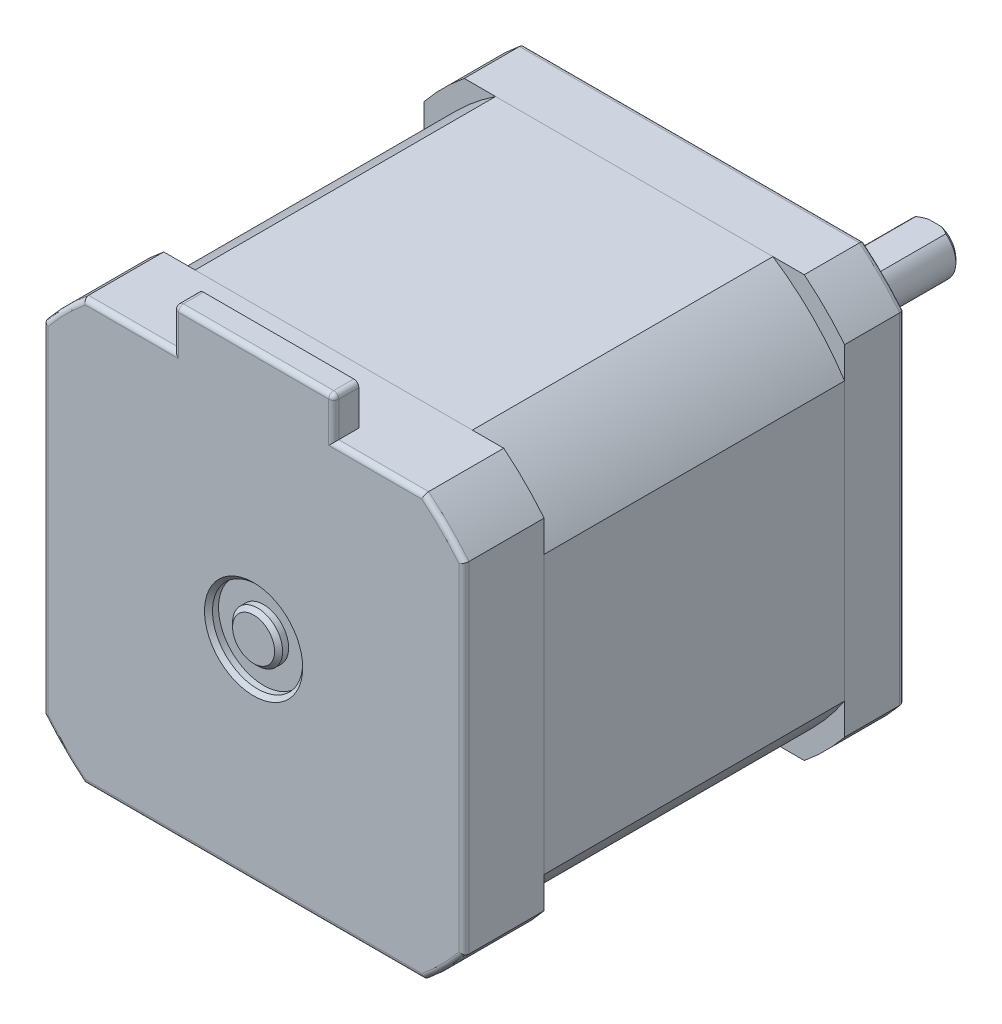
SolidWorks part; units mm, degrees
ref_plane "Plan de face" through (0, 0, 0) normal (0, 0, 1) x (1, 0, 0)
ref_plane "Plan de dessus" through (0, 0, 0) normal (0, 1, 0) x (1, 0, 0)
ref_plane "Plan de droite" through (0, 0, 0) normal (1, 0, 0) x (0, 0, -1)
sketch "Esquisse1" plane through (0, 0, 0) normal (0, 0, 1) x (1, 0, 0)
  line L0 (21, 16.9706) -> (21, -16.9706)
  line L1 (-21, 21) -> (21, 21) construction
  line L2 (-21, 21) -> (-21, -21) construction
  line L3 (-21, -21) -> (21, -21) construction
  line L4 (21, 21) -> (21, -21) construction
  line L5 (-21, 21) -> (21, -21) construction
  line L6 (-21, -21) -> (21, 21) construction
  line L7 (16.9706, -21) -> (-16.9706, -21)
  line L8 (-21, -16.9706) -> (-21, 16.9706)
  line L9 (-16.9706, 21) -> (16.9706, 21)
  arc A0 (-16.9706, 21) -> (-21, 16.9706) centre (0, 0) ccw
  arc A1 (21, 16.9706) -> (16.9706, 21) centre (0, 0) ccw
  arc A2 (-21, -16.9706) -> (-16.9706, -21) centre (0, 0) ccw
  arc A3 (16.9706, -21) -> (21, -16.9706) centre (0, 0) ccw
  point P0 (0, 0)
  dimension "D2" = 54
  dimension "D1" = 42
extrude "Boss.-Extru.1" add sketch "Esquisse1" along normal blind 6
sketch "Esquisse2" plane through (0, 0, 6) normal (0, 0, 1) x (1, 0, 0)
  line L23 (-13.8392, 21) -> (13.8392, 21)
  line L24 (16.9706, 21) -> (-16.9706, 21) construction
  line L25 (21, 13.8392) -> (21, -13.8392)
  line L26 (21, -16.9706) -> (21, 16.9706) construction
  line L27 (13.8392, -21) -> (-13.8392, -21)
  line L28 (-16.9706, -21) -> (16.9706, -21) construction
  line L29 (-21, -13.8392) -> (-21, 13.8392)
  line L30 (-21, 16.9706) -> (-21, -16.9706) construction
  arc A60 (-13.8392, 21) -> (-21, 13.8392) centre (0, 0) ccw
  arc A61 (21, 16.9706) -> (16.9706, 21) centre (0, 0) ccw construction
  arc A62 (21, 13.8392) -> (13.8392, 21) centre (0, 0) ccw
  arc A63 (13.8392, -21) -> (21, -13.8392) centre (0, 0) ccw
  arc A64 (-21, -13.8392) -> (-13.8392, -21) centre (0, 0) ccw
  dimension "D1" = 1.85
extrude "Boss.-Extru.2" add sketch "Esquisse2" along normal blind 30 separate body
sketch "Esquisse3" plane through (0, 0, 36) normal (0, 0, 1) x (1, 0, 0)
  line L0 (-16.9706, -21) -> (16.9706, -21) construction
  line L1 (21, -16.9706) -> (21, 16.9706) construction
  line L2 (16.9706, 21) -> (-16.9706, 21) construction
  line L3 (-21, 16.9706) -> (-21, -16.9706) construction
  line L4 (-16.9706, -21) -> (16.9706, -21)
  line L5 (21, -16.9706) -> (21, 16.9706)
  line L6 (16.9706, 21) -> (-16.9706, 21)
  line L7 (-21, 16.9706) -> (-21, -16.9706)
  arc A0 (-21, -16.9706) -> (-16.9706, -21) centre (0, 0) ccw construction
  arc A1 (16.9706, -21) -> (21, -16.9706) centre (0, 0) ccw construction
  arc A2 (21, 16.9706) -> (16.9706, 21) centre (0, 0) ccw construction
  arc A3 (-16.9706, 21) -> (-21, 16.9706) centre (0, 0) ccw construction
  arc A4 (-21, -16.9706) -> (-16.9706, -21) centre (0, 0) ccw
  arc A5 (16.9706, -21) -> (21, -16.9706) centre (0, 0) ccw
  arc A6 (21, 16.9706) -> (16.9706, 21) centre (0, 0) ccw
  arc A7 (-16.9706, 21) -> (-21, 16.9706) centre (0, 0) ccw
extrude "Boss.-Extru.3" add sketch "Esquisse3" along normal blind 8 separate body
sketch "Esquisse4" plane through (0, 21, 0) normal (0, 1, 0) x (1, 0, 0)
  line L0 (16.9706, -44) -> (-16.9706, -44) construction
  line L1 (8, -44) -> (-8, -44)
  line L2 (8, -44) -> (8, -41.5)
  line L3 (8, -41.5) -> (-8, -41.5)
  line L4 (-8, -44) -> (-8, -41.5)
  line L5 (0, 0) -> (0, -41.5) construction
  dimension "D1" = 2.5
  dimension "D2" = 16
extrude "Boss.-Extru.4" add sketch "Esquisse4" along normal blind 4
sketch "Esquisse5" plane through (0, 0, 0) normal (1, 0, 0) x (0, 0, -1)
  line L0 (0, 0) -> (-78.698, 0) construction
  line L2 (2, 11) -> (0, 11)
  line L3 (2, 11) -> (2, 4.5)
  line L4 (2, 4.5) -> (0, 4.5)
  line L5 (0, 11) -> (0, 4.5)
  line L6 (0, -16.9706) -> (0, 16.9706) construction
  line L7 (24, 0) -> (0, 0)
  line L8 (24, 0) -> (24, 2.5)
  line L9 (24, 2.5) -> (0, 2.5)
  line L10 (0, 0) -> (0, 2.5)
  dimension "D1" = 2
  dimension "D2" = 22
  dimension "D3" = 9
  dimension "D4" = 5
  dimension "D5" = 24
revolve "Révolution1" add sketch "Esquisse5" angle 360 about L0
fillet "Congé1" radius 0.5 14 edges at (-21, 0, 44) (-19.0919, 19.0919, 44) (-12.4853, 21, 44) (-8, 23, 44) (0, 25, 44) (8, 23, 44) (12.4853, 21, 44) (19.0919, 19.0919, 44) (21, 0, 44) (19.0919, -19.0919, 44) (0, -21, 44) (-19.0919, -19.0919, 44) (-8, 25, 42.75) (8, 25, 42.75)
fillet "Congé2" radius 0.5 8 edges at (-19.0919, 19.0919, 0) (-21, 0, 0) (-19.0919, -19.0919, 0) (0, -21, 0) (19.0919, -19.0919, 0) (21, 0, 0) (0, 21, 0) (19.0919, 19.0919, 0) tangent propagation no
chamfer "Chanfrein1" distance 0.4 angle 45 1 edges at (-2.5, 0, -24)
chamfer "Chanfrein2" distance 0.4 angle 45 2 edges at (-4.5, 0, -2) (-11, 0, -2)
sketch "Esquisse6" plane through (0, 0, 0) normal (1, 0, 0) x (0, 0, -1)
  line L0 (0, -2.5) -> (23.6, -2.5) construction
  line L1 (24, 2.5) -> (9, 2.5)
  line L2 (24, 2.5) -> (24, 2)
  line L3 (24, 2) -> (9, 2)
  line L4 (9, 2.5) -> (9, 2)
  line L5 (24, -2.1) -> (24, 2.1) construction
  line L6 (23.6, 2.5) -> (0, 2.5) construction
  dimension "D1" = 4.5
  dimension "D2" = 15
extrude "Enlèv. mat.-Extru.1" cut sketch "Esquisse6" against normal through all both and the other way through all
sketch "Esquisse7" plane through (0, 0, 44) normal (0, 0, 1) x (1, 0, 0)
  circle A0 centre (0, 0) radius 2.5
  circle A1 centre (0, 0) radius 4.5
  dimension "D1" = 5
  dimension "D2" = 9
extrude "Enlèv. mat.-Extru.2" cut sketch "Esquisse7" against normal blind 1
chamfer "Chanfrein3" distance 0.4 angle 45 2 edges at (4.5, 0, 44) (2.5, 0, 44)
hole_wizard "Trou taraudé M31" positions "Esquisse8" profile "Esquisse9" tap size "M3" standard "ISO"
sketch "Esquisse8" plane through (0, 0, 0) normal (0, 0, -1) x (-1, 0, 0)
  line L0 (-15.5, 15.5) -> (15.5, 15.5) construction
  line L1 (15.5, 15.5) -> (15.5, -15.5) construction
  line L2 (15.5, -15.5) -> (-15.5, -15.5) construction
  line L3 (-15.5, -15.5) -> (-15.5, 15.5) construction
  circle A0 centre (0, 0) radius 21.9203 construction
  point P5 (-15.5, 15.5)
  point P6 (15.5, 15.5)
  point P7 (15.5, -15.5)
  point P8 (-15.5, -15.5)
  dimension "D1" = 31
sketch "Esquisse9" plane through (15.5, -15.5, 0) normal (1, 0, 0) x (0, 1, 0)
  line L0 (0, 0) -> (0, 5.7511)
  line L1 (0, 5.7511) -> (1.25, 5)
  line L2 (1.25, 5) -> (1.25, 0)
  line L5 (1.25, 0) -> (0, 0)
  line L10 (0, 5.7511) -> (-1.25, 5) construction
  line L11 (0, -6.35) -> (0, 107.95) construction
  dimension "Diamètre du trou pour taraudage" = 2.5
  dimension "Profondeur du trou pour taraudage" = 5
  dimension "Angle de pointe" = 118
cosmetic thread "Filetage de perçage1" parameters "D1"=5, "D2"=3
cosmetic thread "Filetage de perçage2" parameters "D1"=5, "D2"=3
cosmetic thread "Filetage de perçage3" parameters "D1"=5, "D2"=3
cosmetic thread "Filetage de perçage4" parameters "D1"=5, "D2"=3
